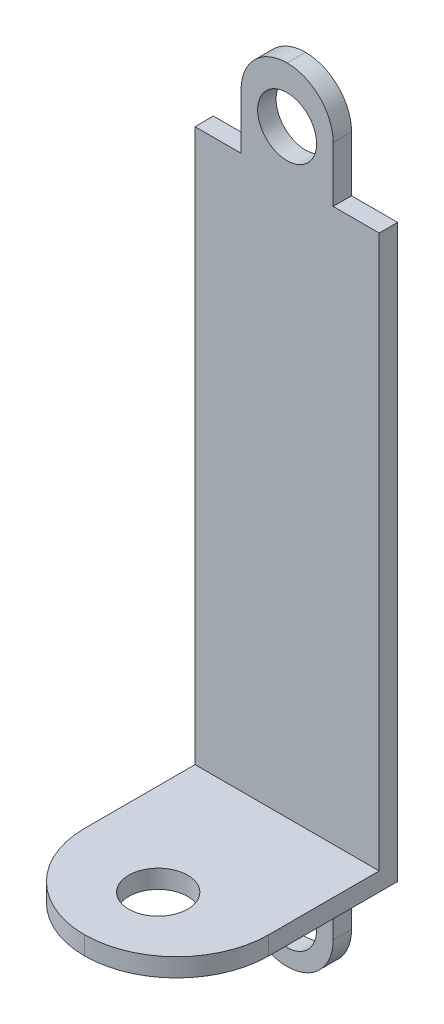
SolidWorks part; units mm, degrees
ref_plane "Front Plane" through (0, 0, 0) normal (0, 0, 1) x (1, 0, 0)
ref_plane "Top Plane" through (0, 0, 0) normal (0, 1, 0) x (1, 0, 0)
ref_plane "Right Plane" through (0, 0, 0) normal (1, 0, 0) x (0, 0, -1)
sketch "Sketch1" plane through (0, 0, 0) normal (0, 0, 1) x (1, 0, 0)
  line L1 (-18.1572, 6.6101) -> (-8.1572, 6.6101)
  line L2 (-18.1572, 6.6101) -> (-18.1572, -29.8899)
  line L3 (-18.1572, -29.8899) -> (-8.1572, -29.8899)
  line L4 (-8.1572, 6.6101) -> (-8.1572, -29.8899)
  dimension "D1" = 36.5
  dimension "D2" = 10
extrude "Boss-Extrude1" add sketch "Sketch1" along normal blind 12
sketch "Sketch2" plane through (-18.1572, 0, 0) normal (-1, 0, 0) x (0, 0, 1)
  line L0 (12, 6.6101) -> (0, 6.6101) construction
  line L1 (0, -29.8899) -> (1, -29.8899)
  line L2 (0, -29.8899) -> (0, 6.6101)
  line L3 (0, 6.6101) -> (1, 6.6101)
  line L4 (1, -29.8899) -> (1, 6.6101)
  line L5 (12, -29.8899) -> (-0.0034, -29.8899)
  line L6 (12, -29.8899) -> (12, -28.8899)
  line L7 (12, -28.8899) -> (-0.0034, -28.8899)
  line L8 (-0.0034, -29.8899) -> (-0.0034, -28.8899)
  line L9 (0, 6.6101) -> (0, -29.8899) construction
  line L10 (12, -29.8899) -> (0, -29.8899) construction
  line L11 (12, 6.6101) -> (12, -29.8899) construction
  line M3 (12, -29.8899) -> (12, 6.6101)
  line M4 (12, 6.6101) -> (0, 6.6101)
  dimension "D1" = 1
  dimension "D2" = 1
extrude "Cut-Extrude1" cut sketch "Sketch2" against normal through all contours L7 L4 M3 M4 region at (-18.1572, -11.1399, 6.5)
sketch "Sketch3" plane through (0, 0, 1) normal (0, 0, 1) x (1, 0, 0)
  line L2 (-13.1572, 11.5981) -> (-13.1572, 34.2826) construction
  line L3 (-18.1572, -29.8899) -> (-8.1572, -29.8899) construction
  line L4 (-8.1572, -28.8899) -> (-8.1572, 6.6101) construction
  circle A0 centre (-13.1572, 3.6101) radius 1.6
  point P2 (4.0928, 1.2899)
  dimension "D1" = 3.2
  dimension "D2" = 33.5
  dimension "D3" = 5
extrude "Cut-Extrude2" cut sketch "Sketch3" against normal blind 16.77
sketch "Sketch4" plane through (0, -28.8899, 0) normal (0, 1, 0) x (1, 0, 0)
  line L1 (-8.1572, -12) -> (-18.1572, -12) construction
  line L2 (-13.1572, 2.6997) -> (-13.1572, -14.2822) construction
  line L4 (-8.1572, -12) -> (-8.1572, 0) construction
  circle A0 centre (-13.1572, -8) radius 1.6
  point P11 (0, 0)
  dimension "D1" = 3.2
  dimension "D2" = 5
  dimension "D4" = 4
extrude "Cut-Extrude4" cut sketch "Sketch4" against normal blind 16.77
fillet "Fillet1" radius 5 1 edges at (-18.1572, -29.3899, 12)
fillet "Fillet2" radius 5 1 edges at (-8.1572, -29.3899, 12)
sketch "Sketch8" plane through (0, -29.8899, 0) normal (0, -1, 0) x (1, 0, 0)
  line L0 (-13.1572, -3.1167) -> (-13.1572, 14.9506) construction
  line L1 (-18.1572, 0) -> (-8.1572, 0) construction
  line L2 (-15.6572, 1) -> (-10.6572, 1)
  line L3 (-15.6572, 1) -> (-15.6572, 0)
  line L4 (-15.6572, 0) -> (-10.6572, 0)
  line L5 (-10.6572, 1) -> (-10.6572, 0)
  line L6 (-15.6572, 1) -> (-10.6572, 0) construction
  line L7 (-15.6572, 0) -> (-10.6572, 1) construction
  line L10 (-8.1572, 7) -> (-8.1572, 0) construction
  point P2 (-13.1572, 0.5)
  point P14 (5.2228, 1)
  point P15 (0, 0)
  dimension "D1" = 1
  dimension "D2" = 5
  dimension "D3" = 0
  dimension "D4" = 5
extrude "Boss-Extrude2" add sketch "Sketch8" along normal blind 6
fillet "Fillet6" radius 2.5 2 edges at (-15.6572, -35.8899, 0.5) (-10.6572, -35.8899, 0.5)
sketch "Sketch9" plane through (0, 0, 1) normal (0, 0, 1) x (1, 0, 0)
  circle A0 centre (-13.1572, -33.3899) radius 1.6
  point P3 (0, 0)
extrude "Cut-Extrude6" cut sketch "Sketch9" against normal up to surface (1 mm away) up to face at (-11.5572, 3.6101, 0)
sketch "Sketch10" plane through (0, 0, 0) normal (0, 0, -1) x (-1, 0, 0)
  line L0 (13.1572, 3.6101) -> (13.1572, 9.4645) construction
  line L1 (8.1572, 6.6101) -> (10.6572, 6.6101)
  line L2 (8.1572, 6.6101) -> (8.1572, 1.1101)
  line L3 (8.1572, 1.1101) -> (10.6572, 1.1101)
  line L4 (10.6572, 6.6101) -> (10.6572, 1.1101)
  line L5 (8.1572, 6.6101) -> (10.6572, 1.1101) construction
  line L6 (8.1572, 1.1101) -> (10.6572, 6.6101) construction
  line L7 (18.1572, 1.1101) -> (15.6572, 6.6101) construction
  line L8 (18.1572, 6.6101) -> (15.6572, 1.1101) construction
  line L9 (15.6572, 6.6101) -> (15.6572, 1.1101)
  line L10 (18.1572, 1.1101) -> (15.6572, 1.1101)
  line L11 (18.1572, 6.6101) -> (18.1572, 1.1101)
  line L12 (18.1572, 6.6101) -> (15.6572, 6.6101)
  point P4 (9.4072, 3.8601)
  point P13 (16.9072, 3.8601)
  dimension "D1" = 5.5
  dimension "D2" = 2.5
extrude "Cut-Extrude7" cut sketch "Sketch10" against normal up to surface (1 mm away) up to face at (-11.5572, 3.6101, 1)
fillet "Fillet7" radius 2.5 2 edges at (-10.6572, 6.6101, 0.5) (-15.6572, 6.6101, 0.5)
